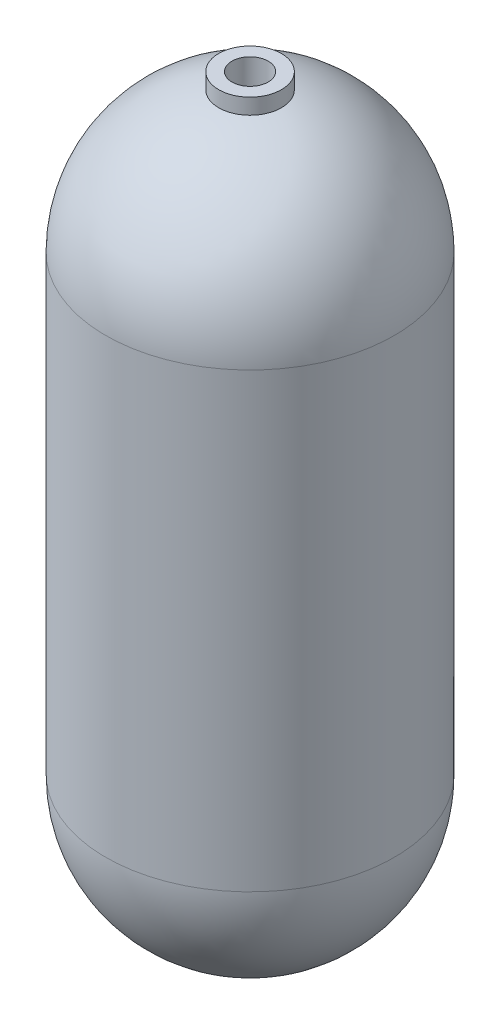
SolidWorks part; units mm, degrees
material "Hexcel AS4C (3000 Filaments)"
ref_plane "Front Plane" through (0, 0, 0) normal (0, 0, 1) x (1, 0, 0)
ref_plane "Top Plane" through (0, 0, 0) normal (0, 1, 0) x (1, 0, 0)
ref_plane "Right Plane" through (0, 0, 0) normal (1, 0, 0) x (0, 0, -1)
sketch "Sketch4" plane through (0, 0, 0) normal (0, 0, 1) x (1, 0, 0)
  line L0 (0, 80.4479) -> (0, -241.4271) construction
  line L1 (12.7, 63.3729) -> (12.7, 57.0229)
  line L3 (58.42, 0) -> (58.42, -183.0071)
  line L4 (52.07, 0) -> (52.07, -183.0071)
  line L5 (0, -235.0771) -> (0, -241.4271)
  line L6 (6.35, 63.3729) -> (12.7, 63.3729)
  line L7 (6.35, 63.3729) -> (2.54, 63.3729)
  line L8 (2.54, 63.3729) -> (2.54, 52.008)
  line L9 (6.35, 63.3729) -> (6.35, 51.6814) construction
  arc A0 (58.42, -183.0071) -> (0, -241.4271) centre (0, -183.0071) cw
  arc A1 (58.42, 0) -> (12.7, 57.0229) centre (0, 0) ccw
  arc A2 (52.07, 0) -> (6.35, 51.6814) centre (0, 0) ccw
  arc A3 (52.07, -183.0071) -> (0, -235.0771) centre (0, -183.0071) cw
  arc A4 (6.35, 51.6814) -> (2.54, 52.008) centre (0, 0) ccw
  dimension "D3" = 304.8
  dimension "D1" = 12.7
  dimension "D2" = 58.42
  dimension "D4" = 6.35
  dimension "D6" = 5.08
  dimension "D5" = 6.35
revolve "Revolve1" add sketch "Sketch4" angle 360 about L0
hole_wizard "5/8-18 Tapped Hole2" positions "Sketch8" profile "Sketch7" tap size "5/8-18" standard "ANSI Inch"
sketch "Sketch8" plane through (0, 63.3729, 0) normal (0, 1, 0) x (1, 0, 0)
  point P0 (0, 0)
sketch "Sketch7" plane through (0, 63.3729, 0) normal (1, 0, 0) x (0, 0, 1)
  line L0 (0, 0) -> (0, 43.2734)
  line L1 (0, 43.2734) -> (7.3419, 38.862)
  line L2 (7.3419, 38.862) -> (7.3419, 0)
  line L5 (7.3419, 0) -> (0, 0)
  line L10 (0, 43.2734) -> (-7.3419, 38.862) construction
  line L11 (0, -6.35) -> (0, 107.95) construction
  dimension "Tap Drill Dia." = 14.6837
  dimension "Tap Drill Depth" = 38.862
  dimension "Drill Angle" = 118
cosmetic thread "Hole Thread1" parameters "D1"=11.8044, "D2"=15.875
ref_axis "Axis1" through (0, -183.0071, 0) along (0, 1, 0)
